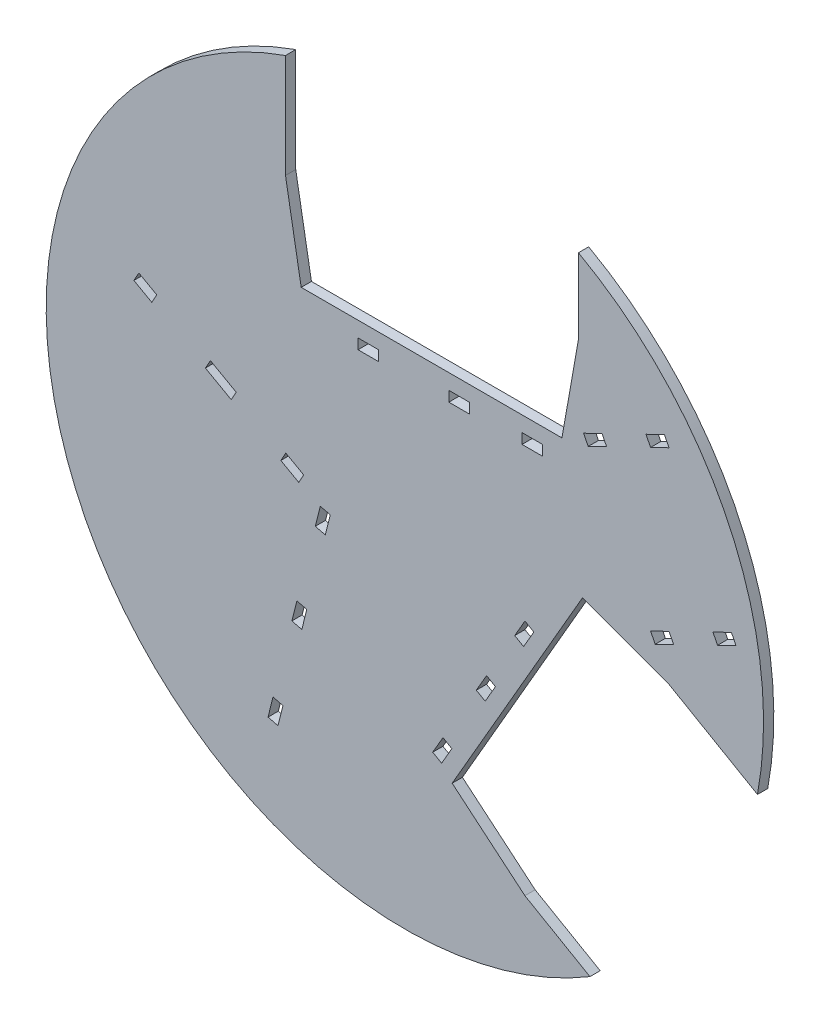
SolidWorks part; units mm, degrees
material "Balsa"
ref_plane "Plan de face" through (0, 0, 0) normal (0, 0, 1) x (1, 0, 0)
ref_plane "Plan de dessus" through (0, 0, 0) normal (0, 1, 0) x (1, 0, 0)
ref_plane "Plan de droite" through (0, 0, 0) normal (1, 0, 0) x (0, 0, -1)
sketch "Esquisse1" plane through (0, 0, 0) normal (0, 0, 1) x (1, 0, 0)
  circle A0 centre (0, 0) radius 175
  dimension "D1" = 350
extrude "Boss.-Extru.1" add sketch "Esquisse1" along normal blind 5
sketch "Esquisse2" plane through (0, 0, 0) normal (0, 0, -1) x (-1, 0, 0)
  line L0 (58.2408, 114.332) -> (58.2408, 213.8766)
  line L1 (58.2408, 213.8766) -> (-84.6817, 213.8766)
  line L2 (-84.6817, 213.8766) -> (-84.6817, 116.5135)
  line L3 (0, 0) -> (-290.6498, 0) construction
  line L4 (-84.6817, 116.5135) -> (-76.6366, 70.8876)
  line L5 (-76.6366, 70.8876) -> (50.5804, 70.8876)
  line L6 (50.5804, 70.8876) -> (58.2408, 114.332)
  line L7 (-128.1349, -6.728) -> (-214.343, -56.5003)
  line L8 (-214.343, -56.5003) -> (-142.8818, -180.2748)
  line L9 (-142.8818, -180.2748) -> (-58.5628, -131.5932)
  line L10 (-58.5628, -131.5932) -> (-23.0722, -101.8131)
  line L11 (-23.0722, -101.8131) -> (-86.6807, 8.3601)
  line L12 (-86.6807, 8.3601) -> (-128.1349, -6.728)
  point P16 (0, 0)
  point P43 (0, 0)
  dimension "D5" = 142.989
  dimension "D6" = 99.5446
  dimension "D1" = 127.217
  dimension "D2" = 100
  dimension "D3" = 100
  dimension "D4" = 142.9225
  dimension "D7" = 70.8876
  dimension "D8" = 50.5804
  dimension "D10" = 120
  dimension "D9" = 2
extrude "Enlèv. mat.-Extru.1" cut sketch "Esquisse2" against normal blind 5
sketch "Esquisse3" plane through (0, 0, 5) normal (0, 0, 1) x (1, 0, 0)
  line L0 (0, 0) -> (0, 103.8673) construction
  line L1 (-49.3567, -7.7578) -> (-58.0775, -2.8643)
  line L2 (-49.3567, -7.7578) -> (-51.8034, -12.1183)
  line L3 (-58.0775, -2.8643) -> (-60.5243, -7.2247)
  line L4 (-51.8034, -12.1183) -> (-60.5243, -7.2247)
  line L5 (-82.2991, 10.7274) -> (-94.8707, 17.7817)
  line L6 (-82.2991, 10.7274) -> (-84.7459, 6.3669)
  line L7 (-94.8707, 17.7817) -> (-97.3175, 13.4213)
  line L8 (-84.7459, 6.3669) -> (-97.3175, 13.4213)
  line L9 (-121.0332, 32.4625) -> (-129.754, 37.356)
  line L10 (-121.0332, 32.4625) -> (-123.48, 28.1021)
  line L11 (-129.754, 37.356) -> (-132.2008, 32.9956)
  line L12 (-123.48, 28.1021) -> (-132.2008, 32.9956)
  line L13 (-36.4119, -18.1392) -> (-38.8398, -27.84)
  line L14 (-36.4119, -18.1392) -> (-41.2623, -16.9253)
  line L15 (-38.8398, -27.84) -> (-43.6902, -26.6261)
  line L16 (0, 0) -> (104.6701, 42.2895) construction
  line L17 (-41.2623, -16.9253) -> (-43.6902, -26.6261)
  line L18 (-47.8487, -63.8364) -> (-50.2765, -73.5372)
  line L19 (-47.8487, -63.8364) -> (-52.6991, -62.6224)
  line L20 (-50.2765, -73.5372) -> (-55.1269, -72.3233)
  line L21 (-52.6991, -62.6224) -> (-55.1269, -72.3233)
  line L22 (-59.4765, -110.2968) -> (-61.9044, -119.9976)
  line L23 (-59.4765, -110.2968) -> (-64.3269, -109.0829)
  line L24 (-61.9044, -119.9976) -> (-66.7548, -118.7837)
  line L25 (-64.3269, -109.0829) -> (-66.7548, -118.7837)
  line L26 (62.9144, -18.0042) -> (58.5843, -15.5042)
  line L27 (62.9144, -18.0042) -> (57.9144, -26.6645)
  line L28 (58.5843, -15.5042) -> (53.5843, -24.1645)
  line L29 (57.9144, -26.6645) -> (53.5843, -24.1645)
  line L30 (39.8511, -47.9511) -> (44.1813, -50.4511)
  line L31 (39.8511, -47.9511) -> (34.8511, -56.6113)
  line L32 (44.1813, -50.4511) -> (39.1813, -59.1113)
  line L33 (34.8511, -56.6113) -> (39.1813, -59.1113)
  line L34 (18.5843, -84.7863) -> (22.9144, -87.2863)
  line L35 (18.5843, -84.7863) -> (13.5843, -93.4465)
  line L36 (22.9144, -87.2863) -> (17.9144, -95.9465)
  line L37 (13.5843, -93.4465) -> (17.9144, -95.9465)
  line L38 (23.0722, -101.8131) -> (86.6807, 8.3601) construction
  line L40 (67.1551, 63.3876) -> (57.1551, 63.3876)
  line L41 (67.1551, 63.3876) -> (67.1551, 58.3876)
  line L42 (67.1551, 58.3876) -> (57.1551, 58.3876)
  line L43 (57.1551, 63.3876) -> (57.1551, 58.3876)
  line L44 (-12.8449, 63.3876) -> (-22.8449, 63.3876)
  line L45 (-12.8449, 63.3876) -> (-12.8449, 58.3876)
  line L46 (-12.8449, 58.3876) -> (-22.8449, 58.3876)
  line L47 (-22.8449, 63.3876) -> (-22.8449, 58.3876)
  line L48 (31.4441, 63.3876) -> (21.4441, 63.3876)
  line L49 (31.4441, 63.3876) -> (31.4441, 58.3876)
  line L50 (31.4441, 58.3876) -> (21.4441, 58.3876)
  line L51 (21.4441, 63.3876) -> (21.4441, 58.3876)
  line L52 (76.6366, 70.8876) -> (-50.5804, 70.8876) construction
  line B0 (122.0981, 6.4136) -> (119.9134, 10.911)
  line B1 (128.9082, 15.2806) -> (119.9134, 10.911)
  line B2 (131.093, 10.7832) -> (122.0981, 6.4136)
  line B3 (131.093, 10.7832) -> (128.9082, 15.2806)
  line B4 (159.3288, 30.0585) -> (150.334, 25.689)
  line B5 (152.5188, 21.1916) -> (150.334, 25.689)
  line B6 (161.5136, 25.5611) -> (159.3288, 30.0585)
  line B7 (161.5136, 25.5611) -> (152.5188, 21.1916)
  line B8 (126.6575, 97.3129) -> (117.6627, 92.9433)
  line B9 (126.6575, 97.3129) -> (128.8423, 92.8154)
  line B10 (117.6627, 92.9433) -> (119.8475, 88.4459)
  line B11 (128.8423, 92.8154) -> (119.8475, 88.4459)
  line B12 (96.2369, 82.5349) -> (98.4217, 78.0375)
  line B13 (96.2369, 82.5349) -> (87.2421, 78.1653)
  line B14 (98.4217, 78.0375) -> (89.4269, 73.6679)
  line B15 (87.2421, 78.1653) -> (89.4269, 73.6679)
  line B16 (87.2421, 78.1653) -> (104.6701, 42.2895) construction
  dimension "D1" = 112.6276
  dimension "D2" = 68
  dimension "D3" = 5
  dimension "D4" = 5
  dimension "D5" = 30.9185
  dimension "D6" = 7.4
  dimension "D7" = 5
  dimension "D8" = 10
  dimension "D9" = 10
  dimension "D10" = 10
  dimension "D11" = 10
  dimension "D12" = 5
  dimension "D13" = 10
  dimension "D14" = 32.5336
  dimension "D15" = 10
  dimension "D16" = 27.4664
  dimension "D17" = 7.5
  dimension "D18" = 10
sketch_block_instance "Bloc1-1"
sketch_block "Bloc1" parameters "D1"=5, "D2"=23.8202, "D3"=39.885, "D4"=10
extrude "Enlèv. mat.-Extru.2" cut sketch "Esquisse3" against normal blind 10
